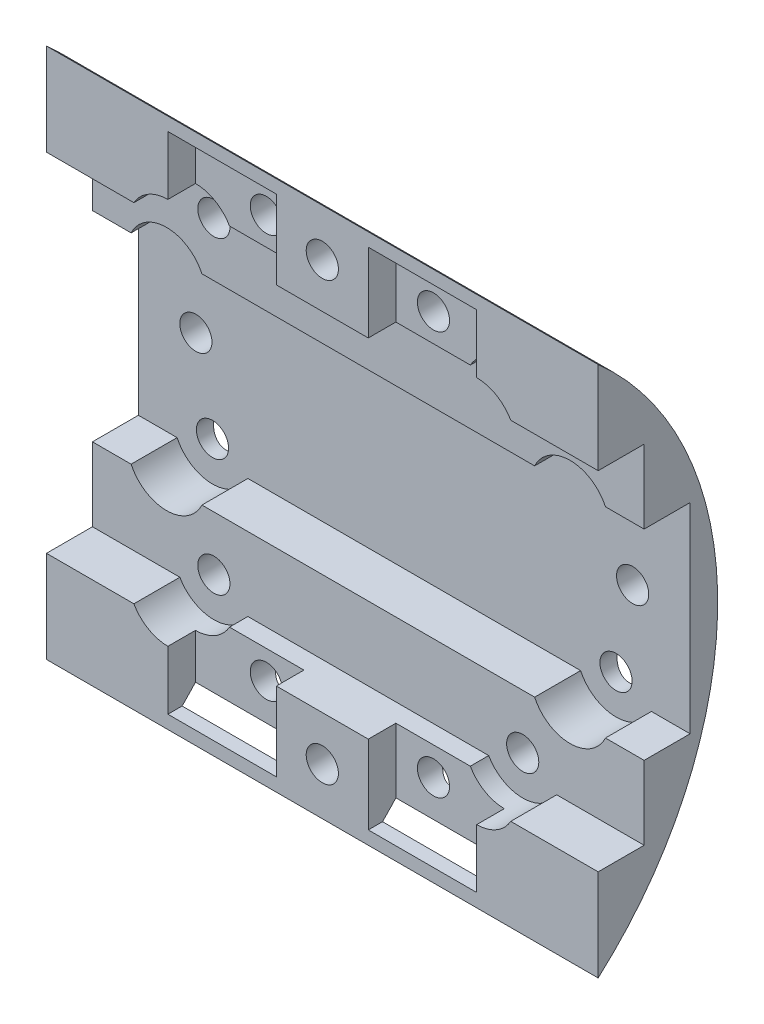
SolidWorks part; units mm, degrees
ref_plane "Front Plane" through (0, 0, 0) normal (0, 0, 1) x (1, 0, 0)
ref_plane "Top Plane" through (0, 0, 0) normal (0, 1, 0) x (1, 0, 0)
ref_plane "Right Plane" through (0, 0, 0) normal (1, 0, 0) x (0, 0, -1)
sketch "Sketch2" plane through (0, 0, 0) normal (0, 0, 1) x (1, 0, 0)
  line L0 (0, 0) -> (0, 26.95) construction
  line L1 (0, 0) -> (0, 23.75) construction
  line L2 (0, 0) -> (9.0887, 21.9421) construction
  circle A0 centre (0, 0) radius 26.95
  circle A1 centre (0, 23.75) radius 1.75
  circle A2 centre (9.0887, 21.9421) radius 1.75
  circle A3 centre (16.7938, 16.7938) radius 1.75
  circle A4 centre (21.9421, 9.0887) radius 1.75
  circle A5 centre (23.75, 0) radius 1.75
  circle A6 centre (21.9421, -9.0887) radius 1.75
  circle A7 centre (16.7938, -16.7938) radius 1.75
  circle A8 centre (9.0887, -21.9421) radius 1.75
  circle A9 centre (0, -23.75) radius 1.75
  circle A10 centre (-9.0887, -21.9421) radius 1.75
  circle A11 centre (-16.7938, -16.7938) radius 1.75
  circle A12 centre (-21.9421, -9.0887) radius 1.75
  circle A13 centre (-23.75, 0) radius 1.75
  circle A14 centre (-21.9421, 9.0887) radius 1.75
  circle A15 centre (-16.7938, 16.7938) radius 1.75
  circle A16 centre (-9.0887, 21.9421) radius 1.75
  dimension "D1" = 53.9
  dimension "D3" = 3.5
  dimension "D2" = 23.75
  dimension "D5" = 22.5
  dimension "D6" = 23.75
  dimension "D4" = 16
sketch "Sketch3" plane through (0, 0, 0) normal (1, 0, 0) x (0, 0, -1)
  line L1 (-30, 0) -> (0, 0) construction
  line L2 (-4.4, 28.8894) -> (-4.4, -28.8894)
  line L3 (-4.4, 10.8894) -> (5.6, 10.8894)
  line L4 (5.6, 10.8894) -> (5.6, -10.8894)
  line L5 (5.6, -10.8894) -> (-4.4, -10.8894)
  line L6 (-4.4, 0) -> (8.6, 0) construction
  line L7 (0.6, -10.8894) -> (0.6, -18.8894)
  line L8 (0.6, -18.8894) -> (-4.4, -18.8894)
  line L9 (0.6, 10.8894) -> (0.6, 18.8894)
  line L10 (0.6, 18.8894) -> (-4.4, 18.8894)
  circle A0 centre (-30, 0) radius 38.6
  dimension "D1" = 77.2
  dimension "D2" = 30
  dimension "D3" = 13
  dimension "D4" = 10
  dimension "D5" = 18
  dimension "D6" = 18
  dimension "D7" = 8
  dimension "D8" = 8
extrude "Boss-Extrude2" add sketch "Sketch3" along normal blind 30 and the other way blind 30 contours L2 A0 L3 L4 L5 region at (0, 15.5968, -4.6602)
extrude "Cut-Extrude3" cut sketch "Sketch2" against normal through all and the other way through all contours A5 | A4 | A3 | A2 | A1 | A16 | A15 | A14 | A13 | A12 | A11 | A10 | A9 | A8 | A7 | A6
sketch "Sketch4" plane through (0, 0, -5.6) normal (0, 0, 1) x (1, 0, 0)
  circle A0 centre (21.9421, -9.0887) radius 1.75 construction
  circle A1 centre (21.9421, 9.0887) radius 1.75 construction
  circle A2 centre (-21.9421, -9.0887) radius 1.75 construction
  circle A3 centre (-21.9421, 9.0887) radius 1.75 construction
  circle A4 centre (21.9421, -9.0887) radius 1.75
  circle A5 centre (21.9421, 9.0887) radius 1.75
  circle A6 centre (-21.9421, -9.0887) radius 1.75
  circle A7 centre (-21.9421, 9.0887) radius 1.75
  circle A8 centre (-21.9421, 9.0887) radius 4.25
  circle A9 centre (-21.9421, -9.0887) radius 4.25
  circle A10 centre (21.9421, 9.0887) radius 4.25
  circle A11 centre (21.9421, -9.0887) radius 4.25
  circle A12 centre (16.7938, -16.7938) radius 1.75 construction
  circle A13 centre (-16.7938, -16.7938) radius 1.75 construction
  circle A14 centre (16.7938, 16.7938) radius 1.75 construction
  circle A15 centre (-16.7938, 16.7938) radius 1.75 construction
  circle A16 centre (16.7938, -16.7938) radius 1.75
  circle A17 centre (-16.7938, -16.7938) radius 1.75
  circle A18 centre (16.7938, 16.7938) radius 1.75
  circle A19 centre (-16.7938, 16.7938) radius 1.75
  circle A20 centre (-16.7938, 16.7938) radius 4.25
  circle A21 centre (16.7938, 16.7938) radius 4.25
  circle A22 centre (16.7938, -16.7938) radius 4.25
  circle A23 centre (-16.7938, -16.7938) radius 4.25
  line M7 (-30, -10.8894) -> (30, -10.8894)
  line M9 (30, 10.8894) -> (-30, 10.8894)
  dimension "D1" = 2.5
  dimension "D2" = 2.5
extrude "Cut-Extrude4" cut sketch "Sketch4" along normal through all contours A8 M9 | A9 M7 | A11 M7 | A10 M9 region at (21.9421, 11.8983, -5.6) region at (-21.9421, 11.8983, -5.6) region at (21.9421, -11.8983, -5.6) region at (-21.9421, -11.8983, -5.6)
extrude "Cut-Extrude5" cut sketch "Sketch4<3>" along normal through all from surface contours A23 A17 | A22 A16 | A20 A19 | A21 A18 region at (-20.9236, 16.7938, -5.6) region at (12.664, 16.7938, -5.6) region at (12.664, -16.7938, -5.6) region at (-20.9236, -16.7938, -5.6) starting at face at (16.7938, -18.5438, -0.6)
sketch "Sketch4<3>" plane through (0, 0, -5.6) normal (0, 0, 1) x (1, 0, 0) same geometry as "Sketch4"
sketch "Sketch5" plane through (0, 0, 4.4) normal (0, 0, 1) x (1, 0, 0)
  line L9 (-5, -18.8894) -> (-5, -28.8894)
  line L10 (-16.7938, 21.0438) -> (-16.7938, 27.4421)
  line L11 (-13.0964, -18.8894) -> (13.0964, -18.8894) construction
  line L12 (-30, -28.8894) -> (30, -28.8894) construction
  line L13 (5, -18.8894) -> (5, -28.8894)
  line L14 (-30, -18.8894) -> (-30, -28.8894) construction
  line L15 (30, -18.8894) -> (30, -28.8894) construction
  line L16 (20.4912, -18.8894) -> (30, -18.8894) construction
  line L17 (-30, -18.8894) -> (-20.4912, -18.8894) construction
  line L18 (20.4912, -18.8894) -> (30, -18.8894)
  line L19 (30, -18.8894) -> (30, -28.8894)
  line L20 (-30, -28.8894) -> (30, -28.8894)
  line L21 (-30, -18.8894) -> (-30, -28.8894)
  line L22 (-30, -18.8894) -> (-20.4912, -18.8894)
  line L23 (-13.0964, -18.8894) -> (13.0964, -18.8894)
  line L24 (-5, 18.8894) -> (-5, 28.8894)
  line L25 (-13.0964, 18.8894) -> (13.0964, 18.8894) construction
  line L26 (-30, 28.8894) -> (30, 28.8894) construction
  line L27 (5, 18.8894) -> (5, 28.8894)
  line L28 (20.4912, 18.8894) -> (30, 18.8894) construction
  line L29 (30, 28.8894) -> (30, 18.8894) construction
  line L30 (-30, 28.8894) -> (-30, 18.8894) construction
  line L31 (-30, 18.8894) -> (-20.4912, 18.8894) construction
  line L32 (-13.0964, 18.8894) -> (13.0964, 18.8894) construction
  line L33 (20.4912, 18.8894) -> (30, 18.8894)
  line L34 (30, 28.8894) -> (30, 18.8894)
  line L35 (-30, 28.8894) -> (30, 28.8894)
  line L36 (-30, 28.8894) -> (-30, 18.8894)
  line L37 (-30, 18.8894) -> (-20.4912, 18.8894)
  line L38 (-13.0964, 18.8894) -> (13.0964, 18.8894)
  line L39 (-16.7938, 27.4421) -> (-5, 27.4421)
  line L40 (-5, 27.4421) -> (5, 27.4421)
  line L41 (5, 27.4421) -> (16.7938, 27.4421)
  line L42 (16.7938, 27.4421) -> (16.7938, 21.0438)
  line L43 (-16.7938, -21.0438) -> (-16.7938, -27.4421)
  line L44 (-16.7938, -27.4421) -> (-5, -27.4421)
  line L45 (-5, -27.4421) -> (5, -27.4421)
  line L46 (5, -27.4421) -> (16.7938, -27.4421)
  line L47 (16.7938, -27.4421) -> (16.7938, -21.0438)
  circle A0 centre (-9.0887, 21.9421) radius 1.75 construction
  arc A1 (13.0964, -18.8894) -> (20.4912, -18.8894) centre (16.7938, -16.7938) ccw construction
  arc A2 (-20.4912, -18.8894) -> (-13.0964, -18.8894) centre (-16.7938, -16.7938) ccw construction
  arc A3 (13.0964, -18.8894) -> (20.4912, -18.8894) centre (16.7938, -16.7938) ccw
  arc A4 (-20.4912, -18.8894) -> (-13.0964, -18.8894) centre (-16.7938, -16.7938) ccw
  arc A5 (20.4912, 18.8894) -> (13.0964, 18.8894) centre (16.7938, 16.7938) ccw construction
  arc A6 (-13.0964, 18.8894) -> (-20.4912, 18.8894) centre (-16.7938, 16.7938) ccw construction
  arc A7 (20.4912, 18.8894) -> (13.0964, 18.8894) centre (16.7938, 16.7938) ccw
  arc A8 (-13.0964, 18.8894) -> (-20.4912, 18.8894) centre (-16.7938, 16.7938) ccw
  circle A9 centre (-9.0887, -21.9421) radius 1.75 construction
  circle M6 centre (9.0887, -21.9421) radius 1.75
  circle M8 centre (-9.0887, -21.9421) radius 1.75
  arc M10 (20.4912, -18.8894) -> (13.0964, -18.8894) centre (16.7938, -16.7938) cw
  line M11 (13.0964, -18.8894) -> (-13.0964, -18.8894)
  arc M12 (-13.0964, -18.8894) -> (-20.4912, -18.8894) centre (-16.7938, -16.7938) cw
  dimension "D1" = 25
  dimension "D2" = 25
  dimension "D3" = 5.5
  dimension "D4" = 5.5
extrude "Cut-Extrude6" cut sketch "Sketch5" against normal blind 3 contours A8 L38 L24 L39 L10 | A7 L42 L41 L27 L38 | L46 L47 L13 M10 M11 M6 | L43 L44 L9 M11 M12 M8 region at (-10.8063, -23.5275, 4.4) region at (10.8063, -23.5275, 4.4) region at (-10.6327, 23.3673, 4.4) region at (10.6327, 23.3673, 4.4)
equation "\"D6@Sketch3\"=\"D5@Sketch3\""
equation "\"D8@Sketch3\"=\"D7@Sketch3\""
equation "\"D2@Sketch5\"=\"D1@Sketch5\""
